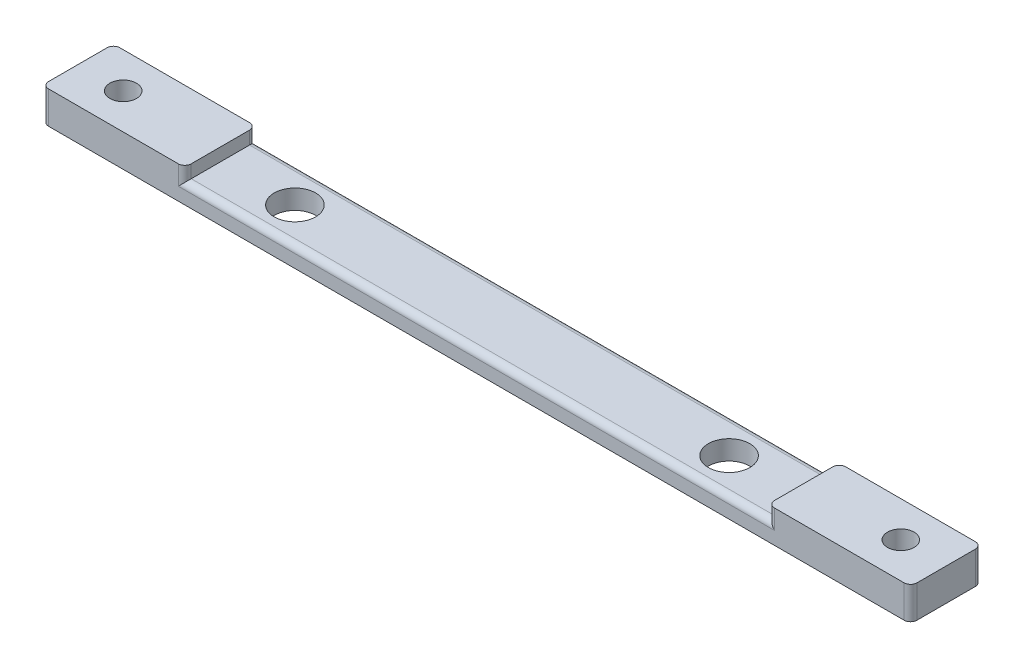
SolidWorks part; units mm, degrees
ref_plane "Plan de face" through (0, 0, 0) normal (0, 0, 1) x (1, 0, 0)
ref_plane "Plan de dessus" through (0, 0, 0) normal (0, 1, 0) x (1, 0, 0)
ref_plane "Plan de droite" through (0, 0, 0) normal (1, 0, 0) x (0, 0, -1)
sketch "Esquisse1" plane through (0, 0, 0) normal (0, 1, 0) x (1, 0, 0)
  line L0 (0, 20.6802) -> (0, -42.2025) construction
  line L1 (0, 0) -> (100.6872, 0) construction
  line L2 (-66, 0) -> (66, 0)
  line L3 (67, 1) -> (67, 10)
  line L4 (66, 11) -> (-66, 11)
  line L5 (24.5168, 5.5) -> (0.5615, 5.5) construction
  line L6 (-67, 1) -> (-67, 10)
  circle A0 centre (60, 5.5) radius 2.05
  circle A1 centre (33.5, 5.5) radius 3.2
  arc A2 (66, 0) -> (67, 1) centre (66, 1) ccw
  arc A3 (67, 10) -> (66, 11) centre (66, 10) ccw
  arc A4 (-67, 10) -> (-66, 11) centre (-66, 10) cw
  arc A5 (-66, 0) -> (-67, 1) centre (-66, 1) cw
  circle A6 centre (-33.5, 5.5) radius 3.2
  circle A7 centre (-60, 5.5) radius 2.05
  point P1 (-67, 11)
  point P9 (0, 0)
  point P17 (67, 0)
  point P20 (67, 11)
  point P31 (0, 11)
  point P32 (-67, 0)
  dimension "D1" = 67
  dimension "D5" = 1
  dimension "D6" = 6.4
  dimension "D7" = 4.1
  dimension "D2" = 33.5
  dimension "D3" = 60
  dimension "D4" = 11
extrude "Boss.-Extru.1" add sketch "Esquisse1" along normal blind 5
sketch "Esquisse2" plane through (0, 0, 0) normal (0, 0, 1) x (1, 0, 0)
  line L0 (0, 18.1819) -> (0, -11.7321) construction
  line L1 (-16.5133, 3) -> (14.2481, 3) construction
  line L2 (-45, 5) -> (-45, 3)
  line L3 (45, 5) -> (45, 3)
  line L4 (-66, 0) -> (66, 0)
  line L5 (66, 0) -> (66, 5)
  line L6 (66, 5) -> (-66, 5)
  line L7 (-66, 5) -> (-66, 0)
  line L8 (-66, 0) -> (66, 0)
  line L9 (66, 0) -> (66, 5)
  line L10 (66, 5) -> (-66, 5)
  line L11 (-66, 5) -> (-66, 0)
  line L12 (-45, 3) -> (45, 3)
  point P13 (0, 3)
  line M10 (66, 5) -> (-66, 5)
  dimension "D2" = 3
  dimension "D3" = 45
  dimension "D1" = 0
extrude "Enlèv. mat.-Extru.1" cut sketch "Esquisse2" against normal through all contours L2 L12 L3 M10 region at (0, 4, 0)
fillet "Congé1" radius 1 6 edges at (0, 3, -11) (45, 4, -11) (45, 4, 0) (0, 3, 0) (-45, 4, -11) (-45, 4, 0)
